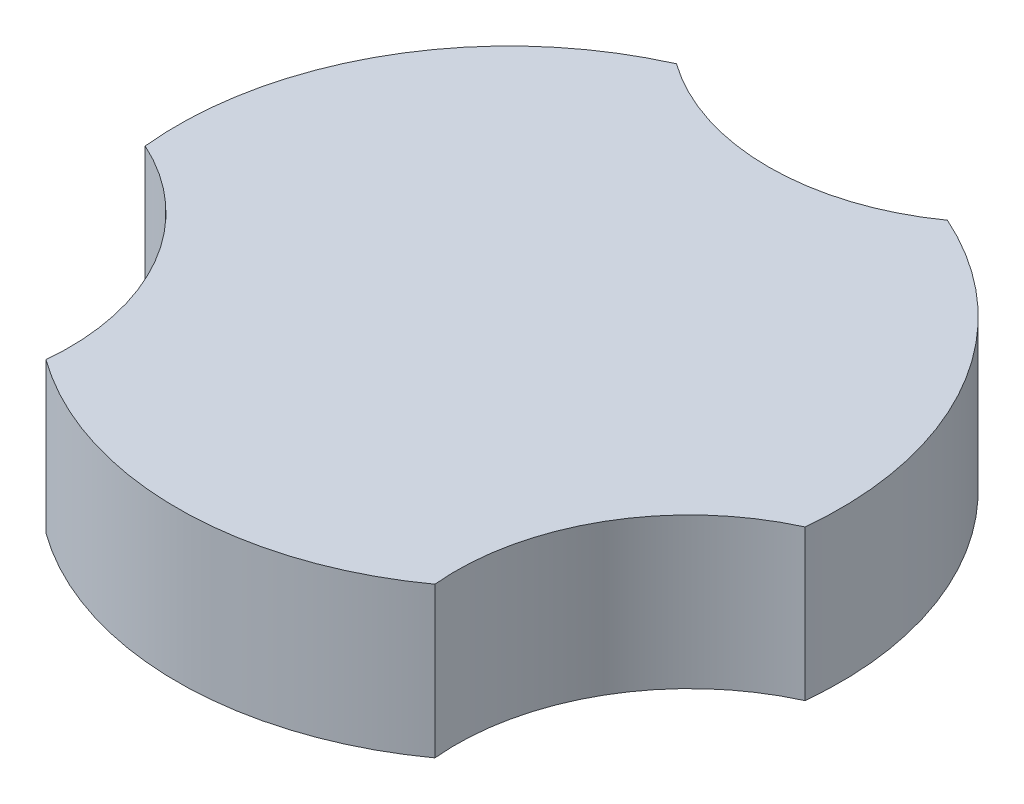
SolidWorks part; units mm, degrees
ref_plane "Front Plane" through (0, 0, 0) normal (0, 0, 1) x (1, 0, 0)
ref_plane "Top Plane" through (0, 0, 0) normal (0, 1, 0) x (1, 0, 0)
ref_plane "Right Plane" through (0, 0, 0) normal (1, 0, 0) x (0, 0, -1)
sketch "Lens Sketch" plane through (0, 0, 0) normal (0, 1, 0) x (1, 0, 0)
  circle A0 centre (0, 0) radius 14
  circle A1 centre (0, 0) radius 14 construction
  circle A2 centre (0, 20.8) radius 9.85
  circle A3 centre (18.0133, -10.4) radius 9.85
  circle A4 centre (-18.0133, -10.4) radius 9.85
  point P7 (0, 0)
  point P8 (0, 0)
  point P12 (0, 0)
  dimension "D1" = 28
  dimension "D2" = 28
  dimension "D3" = 19.7
  dimension "D4" = 20.8
  dimension "D5" = 3
extrude "Lens" add sketch "Lens Sketch" along normal blind 6.35 contours A4 A0 A3 A2 region at (0, 0, 0)
